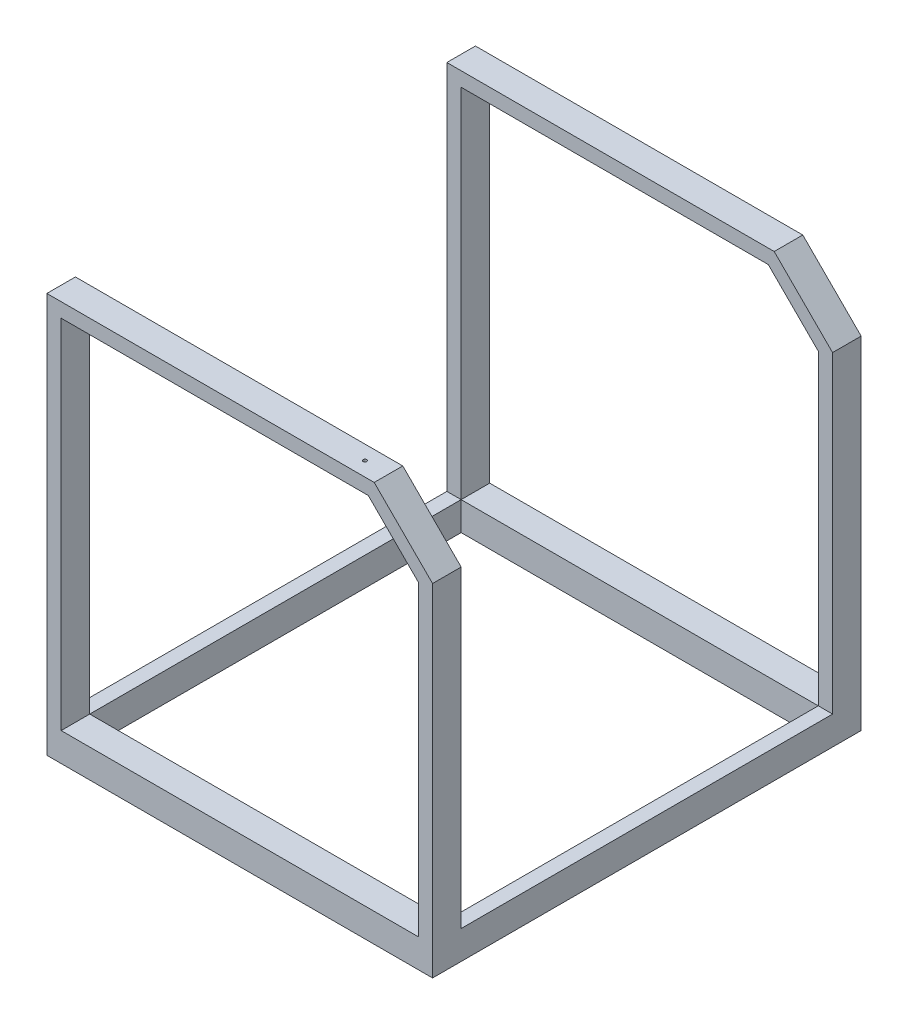
SolidWorks part; units mm, degrees
ref_plane "Front Plane" through (0, 0, 0) normal (0, 0, 1) x (1, 0, 0)
ref_plane "Top Plane" through (0, 0, 0) normal (0, 1, 0) x (1, 0, 0)
ref_plane "Right Plane" through (0, 0, 0) normal (1, 0, 0) x (0, 0, -1)
sketch "Sketch1" plane through (0, 0, 0) normal (0, 0, 1) x (1, 0, 0)
  line L0 (0, 0) -> (0, 560)
  line L1 (0, 560) -> (458.2843, 560)
  line L2 (540, 478.2843) -> (540, 0)
  line L3 (540, 0) -> (0, 0)
  line L4 (20, 40) -> (20, 540)
  line L5 (20, 540) -> (450, 540)
  line L6 (520, 470) -> (520, 40)
  line L7 (520, 40) -> (20, 40)
  line L8 (450, 540) -> (520, 470)
  line L9 (458.2843, 560) -> (540, 478.2843)
  point P4 (540, 560)
  point P8 (520, 540)
  dimension "D1" = 20
  dimension "D2" = 40
  dimension "D3" = 20
  dimension "D4" = 20
  dimension "D5" = 430
  dimension "D6" = 20
  dimension "D8" = 500
extrude "Boss-Extrude1" add sketch "Sketch1" along normal blind 40
sketch "Sketch2" plane through (0, 0, 40) normal (0, 0, 1) x (1, 0, 0)
  line L1 (540, 0) -> (520, 0)
  line L2 (540, 0) -> (540, 40)
  line L3 (540, 40) -> (520, 40)
  line L4 (520, 0) -> (520, 40)
  line L5 (0, 0) -> (20, 0)
  line L6 (0, 0) -> (0, 40)
  line L7 (0, 40) -> (20, 40)
  line L8 (20, 0) -> (20, 40)
extrude "Boss-Extrude2" add sketch "Sketch2" along normal blind 520
ref_plane "Plane1" through (0, 0, 300) normal (0, 0, -1) x (-1, 0, 0)
mirror "Mirror1" about plane through (0, 0, 300) normal (0, 0, -1) of "Boss-Extrude1"
sketch "Sketch3" plane through (0, 560, 0) normal (0, 1, 0) x (1, 0, 0)
  line L0 (458.2843, -560) -> (458.2843, -600) construction
  circle A0 centre (425.2843, -580) radius 2.5
  dimension "D1" = 5
  dimension "D2" = 33
extrude "Cut-Extrude1" cut sketch "Sketch3" against normal blind 61
